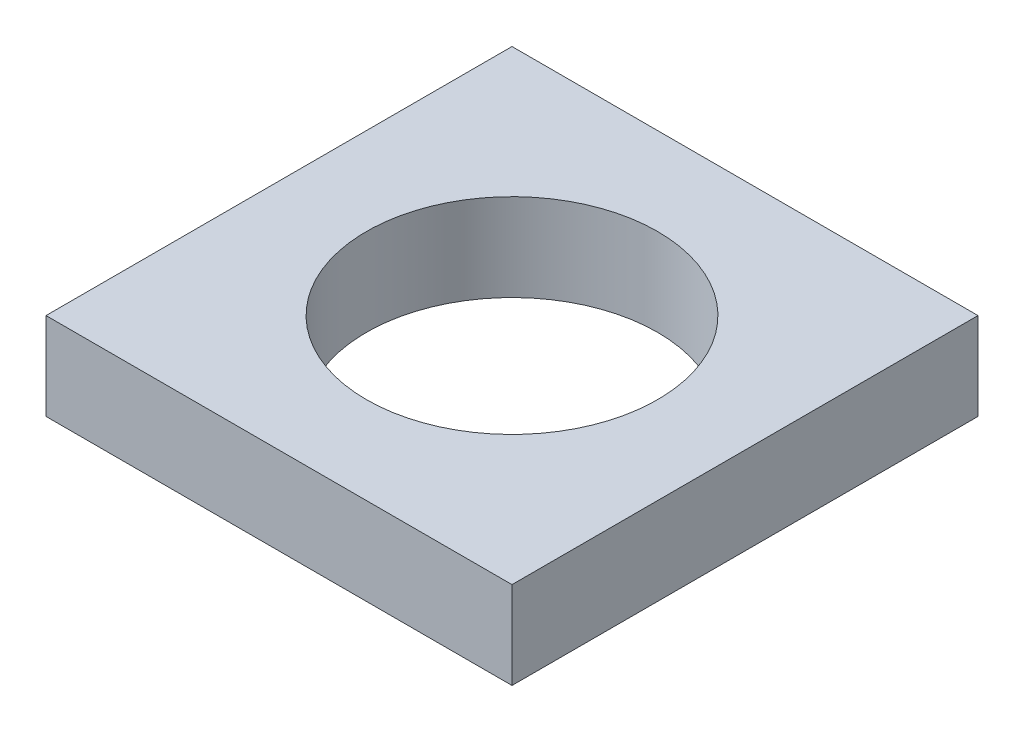
SolidWorks part; units mm, degrees
ref_plane "Front Plane" through (0, 0, 0) normal (0, 0, 1) x (1, 0, 0)
ref_plane "Top Plane" through (0, 0, 0) normal (0, 1, 0) x (1, 0, 0)
ref_plane "Right Plane" through (0, 0, 0) normal (1, 0, 0) x (0, 0, -1)
sketch "Sketch2" plane through (0, 0, 0) normal (0, 1, 0) x (1, 0, 0)
  circle A0 centre (0, 0) radius 40.005
  circle A1 centre (0, 0) radius 42.4942
  circle A2 centre (0, 0) radius 37.9984
  circle A3 centre (0, 0) radius 40.5003
  dimension "D1" = 80.01
  dimension "D2" = 84.9884
  dimension "D3" = 75.9968
  dimension "D4" = 81.0006
extrude "Boss-Extrude1" add sketch "Sketch2" along normal blind 9.525 contours A1 A3 | A3 A0 region at (-41.2923, 0, 0) region at (-40.3857, 0, 0)
extrude "Boss-Extrude2" add sketch "Sketch2<4>" along normal blind 2.54 contours A0 A2 region at (-38.8735, 0, 0)
sketch "Sketch2<4>" plane through (0, 0, 0) normal (0, 1, 0) x (1, 0, 0) same geometry as "Sketch2"
extrude "Boss-Extrude3" add sketch "Sketch2<5>" against normal blind 7.62 contours A0 A2 | A3 A0 region at (-38.8735, 0, 0) region at (-40.3857, 0, 0)
sketch "Sketch2<5>" plane through (0, 0, 0) normal (0, 1, 0) x (1, 0, 0) same geometry as "Sketch2"
sketch "Sketch3" plane through (0, 0, 0) normal (0, 1, 0) x (1, 0, 0)
  line L1 (50.8, 50.8) -> (-50.8, 50.8)
  line L2 (50.8, 50.8) -> (50.8, -50.8)
  line L3 (50.8, -50.8) -> (-50.8, -50.8)
  line L4 (-50.8, 50.8) -> (-50.8, -50.8)
  line L5 (50.8, 50.8) -> (-50.8, -50.8) construction
  line L6 (50.8, -50.8) -> (-50.8, 50.8) construction
  circle A0 centre (0, 0) radius 31.75
  point P0 (0, 0)
  dimension "D3" = 63.5
  dimension "D1" = 101.6
  dimension "D2" = 101.6
extrude "Boss-Extrude4" add sketch "Sketch3" along normal blind 10.16 and the other way blind 8.89 separate body
